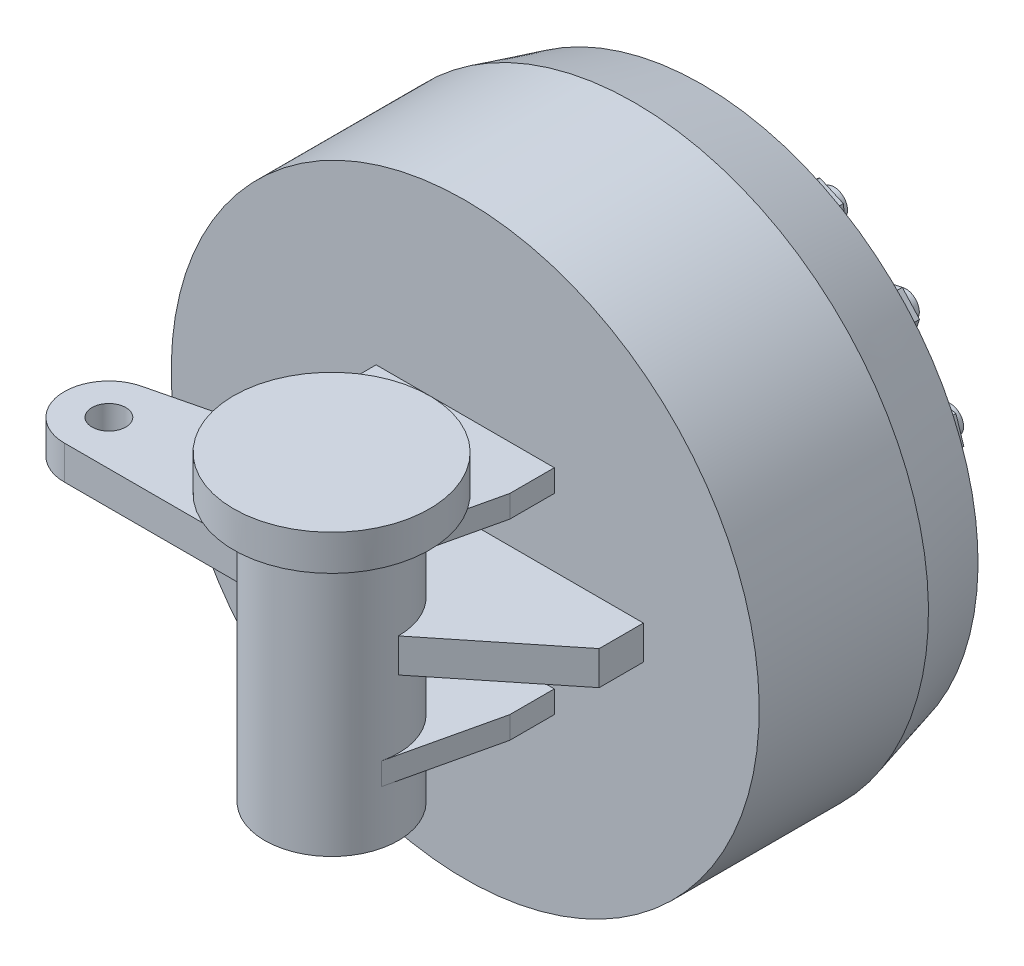
SolidWorks part; units mm, degrees
ref_plane "Front Plane" through (0, 0, 0) normal (0, 0, 1) x (1, 0, 0)
ref_plane "Top Plane" through (0, 0, 0) normal (0, 1, 0) x (1, 0, 0)
ref_plane "Right Plane" through (0, 0, 0) normal (1, 0, 0) x (0, 0, -1)
sketch "Sketch1" plane through (0, 0, 0) normal (1, 0, 0) x (0, 0, -1)
  line L0 (0, 0) -> (0, 165)
  line L1 (0, 165) -> (95, 165)
  line L2 (95, 165) -> (133, 154.8179)
  line L3 (133, 154.8179) -> (133, 75)
  line L4 (133, 75) -> (158, 75)
  line L5 (158, 75) -> (158, 50)
  line L6 (158, 50) -> (183, 50)
  line L7 (183, 50) -> (183, 0)
  line L8 (183, 0) -> (0, 0)
  dimension "D1" = 165
  dimension "D2" = 25
  dimension "D3" = 95
  dimension "D4" = 38
  dimension "D5" = 25
  dimension "D6" = 15
  dimension "D7" = 25
  dimension "D8" = 50
revolve "Revolve1" add sketch "Sketch1" angle 360 about L8
chamfer "Chamfer1" distance 4 angle 45 1 edges at (0, 50, -183)
fillet "Fillet1" radius 3.5 2 edges at (0, 75, -158) (0, 50, -158)
sketch "Sketch2" plane through (0, 0, 0) normal (0, 1, 0) x (1, 0, 0)
  circle A0 centre (0, -75) radius 37.5
  point P2 (0, 0)
  dimension "D1" = 75
  dimension "D2" = 75
extrude "Boss-Extrude1" add sketch "Sketch2" against normal blind 90 and the other way blind 80 separate body
sketch "Sketch3" plane through (0, 0, 0) normal (0, 1, 0) x (1, 0, 0)
  line L0 (-50, 0) -> (50, 0)
  line L1 (50, 0) -> (50, -25)
  line L2 (50, -25) -> (36.543, -83.418)
  line L3 (0, 0) -> (0, -132.7785) construction
  line L4 (-50, -25) -> (-36.543, -83.418)
  line L5 (-50, 0) -> (-50, -25)
  line L6 (-36.543, -83.418) -> (36.543, -83.418)
  circle A0 centre (0, -75) radius 37.5 construction
  dimension "D1" = 50
  dimension "D2" = 25
extrude "Boss-Extrude2" add sketch "Sketch3" against normal blind 12.5 from offset 60
mirror "Mirror1" about plane through (0, 0, 0) normal (0, 1, 0) of "Boss-Extrude2"
sketch "Sketch4" plane through (0, 0, 0) normal (0, 1, 0) x (1, 0, 0)
  line L0 (-50, 0) -> (100, 0)
  line L1 (-165, 0) -> (165, 0) construction
  line L2 (100, 0) -> (100, -24.8329)
  line L3 (0, -75) -> (134.4228, -75) construction
  line L4 (100, -24.8329) -> (37.5, -75)
  line L5 (-37.5, -75) -> (-150, -75)
  line L6 (-155.8972, -25.7055) -> (-50, 0)
  arc A0 (36.543, -83.418) -> (-36.543, -83.418) centre (0, -75) ccw construction
  circle A1 centre (0, -75) radius 37.5 construction
  arc A2 (-150, -75) -> (-155.8972, -25.7055) centre (-150, -50) cw
  arc A3 (-37.5, -75) -> (37.5, -75) centre (0, -75) ccw
  circle A4 centre (-150, -50) radius 9.5
  point P18 (0, 0)
  dimension "D3" = 25
  dimension "D4" = 19
  dimension "D1" = 150
  dimension "D2" = 150
extrude "Boss-Extrude3" add sketch "Sketch4" along normal mid plane 19
sketch "Sketch5" plane through (0, 60, 0) normal (0, 1, 0) x (1, 0, 0)
  circle A0 centre (0, -75) radius 55
  dimension "D1" = 110
extrude "Boss-Extrude4" add sketch "Sketch5" along normal up to surface (20 mm away) up to face at (0, 80, 112.5)
sketch "Sketch6" plane through (0, 0, -133) normal (0, 0, -1) x (-1, 0, 0)
  line L1 (6.9443, 107.5) -> (14.1612, 120)
  line L2 (14.1612, 120) -> (6.9443, 132.5)
  line L3 (6.9443, 132.5) -> (-7.4895, 132.5)
  line L4 (-7.4895, 132.5) -> (-14.7063, 120)
  line L5 (-14.7063, 120) -> (-7.4895, 107.5)
  line L6 (-7.4895, 107.5) -> (6.9443, 107.5)
  circle A0 centre (-0.2726, 120) radius 12.5 construction
  circle A1 centre (-0.2726, 120) radius 7.5
  point P1 (-0.2726, 132.5)
  dimension "D2" = 15
  dimension "D1" = 25
  dimension "D3" = 120
extrude "Boss-Extrude5" add sketch "Sketch6" along normal blind 25 contours A1 region at (0.2726, 120, -133)
extrude "Boss-Extrude6" add sketch "Sketch6<3>" along normal blind 12.5 from offset 6 contours L5 L6 L1 L2 L3 L4 A1 region at (0.2726, 107.8819, -133)
sketch "Sketch6<3>" plane through (0, 0, -133) normal (0, 0, -1) x (-1, 0, 0) same geometry as "Sketch6"
pattern_circular "CirPattern1" count 15 over 360 about axis through (0, 0, -158) along (0, 0, -1) of "Boss-Extrude6", "Boss-Extrude5"
